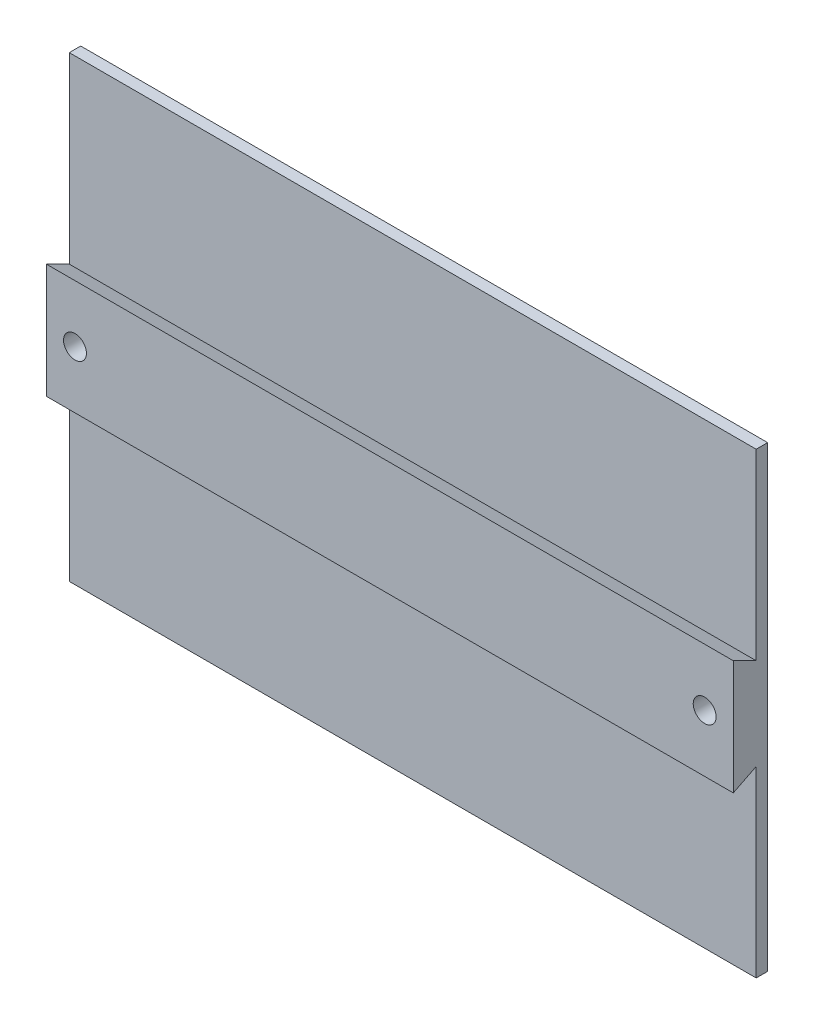
SolidWorks part; units mm, degrees
ref_plane "Front Plane" through (0, 0, 0) normal (1, 0, 0) x (0, 1, 0)
ref_plane "Top Plane" through (0, 0, 0) normal (0, 0, 1) x (0, 1, 0)
ref_plane "Right Plane" through (0, 0, 0) normal (0, 1, 0) x (-1, 0, 0)
sketch "Sketch1" plane through (0, 0, 0) normal (0, 0, 1) x (0, 1, 0)
  line L1 (-20, -30) -> (20, -30)
  line L2 (-20, -30) -> (-20, 30)
  line L3 (-20, 30) -> (20, 30)
  line L4 (20, -30) -> (20, 30)
  line L5 (-20, -30) -> (20, 30) construction
  line L6 (-20, 30) -> (20, -30) construction
  line L7 (-5, 30) -> (5, 30)
  line L8 (-5, 30) -> (-5, -30)
  line L9 (-5, -30) -> (5, -30)
  line L10 (5, 30) -> (5, -30)
  line L11 (-5, 30) -> (5, -30) construction
  line L12 (-5, -30) -> (5, 30) construction
  point P0 (0, 0)
  point P6 (0, 0)
  dimension "D1" = 40
  dimension "D2" = 60
  dimension "D3" = 10
extrude "Boss-Extrude1" add sketch "Sketch1" along normal blind 1 contours L8 L3 L2 L1 | L3 L10 L1 L4 region at (0, -12.5, 0) region at (0, 12.5, 0)
extrude "Boss-Extrude2" add sketch "Sketch1<3>" along normal blind 3 contours L10 L3 L8 L1 region at (0, 0, 0)
sketch "Sketch1<3>" plane through (0, 0, 0) normal (0, 0, 1) x (0, 1, 0) same geometry as "Sketch1"
sketch "Sketch2" plane through (30, 0, 0) normal (1, 0, 0) x (0, 1, 0)
  line L0 (-5, 1) -> (-4, 1)
  line L1 (5, 1) -> (4, 1)
  line L2 (-5, 3) -> (-4, 1)
  line L3 (4, 1) -> (5, 3)
  line L4 (-5, 1) -> (-5, 3)
  line L5 (5, 1) -> (5, 3)
extrude "Cut-Extrude1" cut sketch "Sketch2" against normal blind 66
sketch "Sketch5" plane through (0, 0, 3) normal (0, 0, 1) x (1, 0, 0)
  circle A0 centre (-27.5, 0) radius 1
  circle A1 centre (27.5, 0) radius 1
extrude "Cut-Extrude2" cut sketch "Sketch5" against normal blind 10
